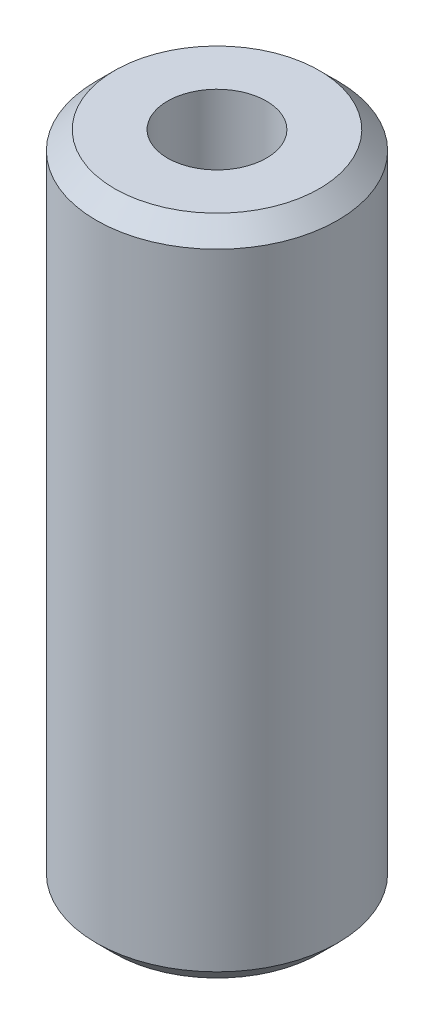
SolidWorks part; units mm, degrees
ref_plane "Front Plane" through (0, 0, 0) normal (0, 0, 1) x (1, 0, 0)
ref_plane "Top Plane" through (0, 0, 0) normal (0, 1, 0) x (1, 0, 0)
ref_plane "Right Plane" through (0, 0, 0) normal (1, 0, 0) x (0, 0, -1)
sketch "Sketch1" plane through (0, 0, 0) normal (0, 1, 0) x (1, 0, 0)
  circle A0 centre (0, 0) radius 10
  dimension "SHAFT_OD" = 20
extrude "Boss-Extrude1" add sketch "Sketch1" along normal blind 54.8903
sketch "Sketch2" plane through (0, 0, 0) normal (0, 1, 0) x (1, 0, 0)
  circle A0 centre (0, 0) radius 4.0988
  dimension "BORE_D" = 8.1976
extrude "Cut-Extrude1" cut sketch "Sketch2" along normal through all
chamfer "Chamfer1" distance 1.5157 angle 45 2 edges at (0, 54.8903, 10) (0, 0, 10)
